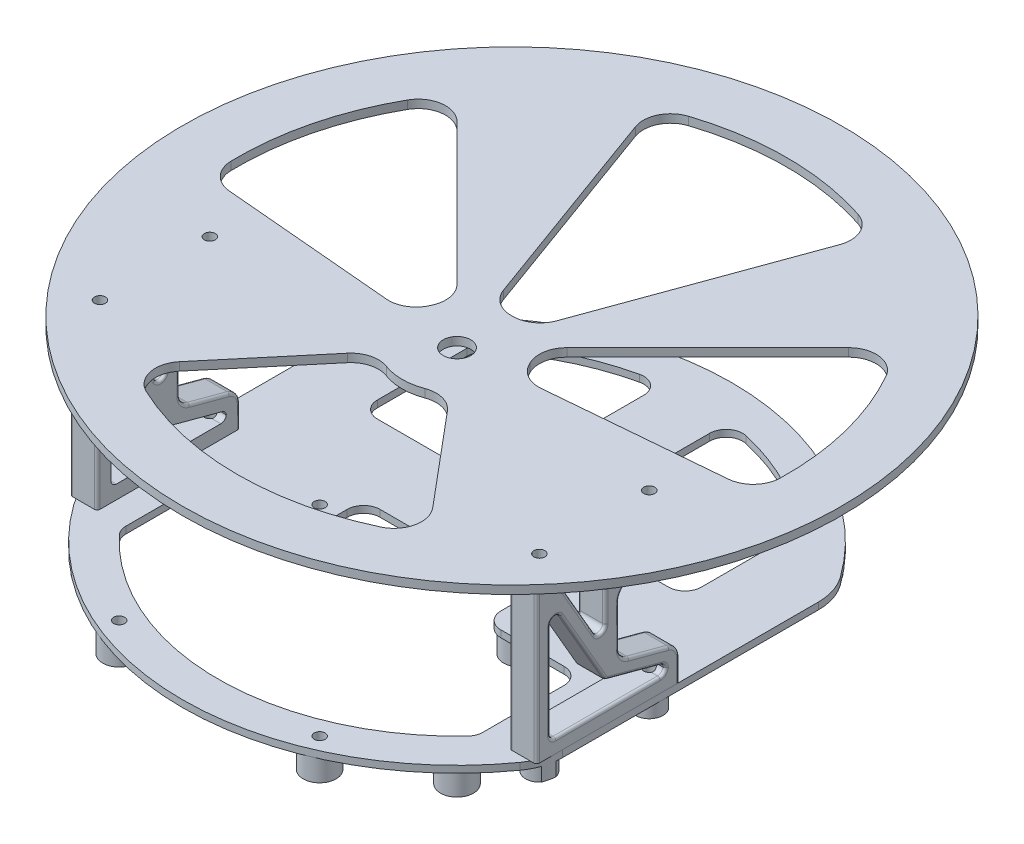
SolidWorks part; units mm, degrees
ref_plane "Front" through (0, 0, 0) normal (0, 0, 1) x (1, 0, 0)
ref_plane "Top" through (0, 0, 0) normal (0, 1, 0) x (1, 0, 0)
ref_plane "Right" through (0, 0, 0) normal (1, 0, 0) x (0, 0, -1)
sketch "Sketch1" plane through (0, 0, 0) normal (0, 1, 0) x (1, 0, 0)
  line L0 (0, 71.1393) -> (0, -87.7098) construction
  line L1 (-42.5, 26.3391) -> (-42.5, -26.3391)
  line L2 (42.5, 26.3391) -> (42.5, -26.3391)
  arc A0 (-42.5, -26.3391) -> (42.5, -26.3391) centre (0, 0) ccw
  arc A1 (42.5, 26.3391) -> (-42.5, 26.3391) centre (0, 0) ccw
  dimension "D1" = 100
  dimension "D2" = 85
extrude "Boss-Extrude1" add sketch "Sketch1" along normal blind 1.25
sketch "Sketch2" plane through (0, 0, 0) normal (0, -1, 0) x (1, 0, 0)
  line L0 (0, 45.5144) -> (0, -63.1722) construction
  line L1 (-51.2989, 0) -> (55.2567, 0) construction
  circle A0 centre (-33, 33) radius 3
  circle A2 centre (-33, 33) radius 1.125
  circle A4 centre (-33, -33) radius 1.125
  circle A5 centre (-33, -33) radius 3
  circle A6 centre (33, -33) radius 3
  circle A7 centre (33, -33) radius 1.125
  circle A8 centre (33, 33) radius 1.125
  circle A9 centre (33, 33) radius 3
  dimension "D3" = 2.25
  dimension "D4" = 6
  dimension "D1" = 66
  dimension "D2" = 66
extrude "Boss-Extrude2" add sketch "Sketch2" along normal blind 4
fillet "Fillet1" radius 10 4 edges at (-42.5, 0.625, -26.3391) (-42.5, 0.625, 26.3391) (42.5, 0.625, -26.3391) (42.5, 0.625, 26.3391)
sketch "Sketch3" plane through (0, 1.25, 0) normal (0, 1, 0) x (1, 0, 0)
  line L0 (0, 58.0627) -> (0, -62.1815) construction
  line L1 (-18.25, -6.75) -> (18.25, -6.75) construction
  line L2 (-18.25, -6.75) -> (-18.25, -43.25) construction
  line L3 (-18.25, -43.25) -> (18.25, -43.25) construction
  line L4 (18.25, -6.75) -> (18.25, -43.25) construction
  line L5 (-18.25, -6.75) -> (18.25, -43.25) construction
  line L6 (-18.25, -43.25) -> (18.25, -6.75) construction
  circle A0 centre (-18.25, -6.75) radius 1
  circle A1 centre (18.25, -6.75) radius 1
  circle A2 centre (18.25, -43.25) radius 1
  circle A3 centre (-18.25, -43.25) radius 1
  circle A4 centre (-40, -5) radius 1
  circle A5 centre (-40, -25) radius 1
  circle A6 centre (40, -25) radius 1
  circle A7 centre (40, -5) radius 1
  point P0 (0, -25)
  dimension "D1" = 2
  dimension "D2" = 36.5
  dimension "D3" = 25
  dimension "D4" = 20
  dimension "D5" = 80
  dimension "D6" = 0
sketch "Sketch4" plane through (0, 0, 0) normal (0, -1, 0) x (1, 0, 0)
  circle A0 centre (-18.25, 43.25) radius 3
  circle A1 centre (18.25, 43.25) radius 3
  circle A2 centre (18.25, 6.75) radius 3
  circle A3 centre (-18.25, 6.75) radius 3
  circle A4 centre (-40, 25) radius 2.5
  circle A5 centre (-40, 5) radius 2.5
  circle A6 centre (40, 25) radius 2.5
  circle A7 centre (40, 5) radius 2.5
  arc M10 (42.5, 23.3184) -> (40.625, 29.1481) centre (32.5, 23.3184) ccw
  arc M16 (-40.625, 29.1481) -> (-42.5, 23.3184) centre (-32.5, 23.3184) ccw
  dimension "D1" = 6
  dimension "D2" = 5
extrude "Boss-Extrude3" add sketch "Sketch4" along normal up to surface (4 mm away) contours A3 | A0 | A1 | A2 region at (-18.25, 0, 43.25) region at (18.25, 0, 43.25) region at (18.25, 0, 6.75) region at (-18.25, 0, 6.75) up to face at (-33, -4, 30)
extrude "Boss-Extrude7" add sketch "Sketch4<3>" along normal offset from surface (2.5 mm away) 1.5 contours A4 M16 | A6 M10 | A5 | A7 region at (-39.9675, 0, 24.9927) region at (39.9675, 0, 24.9927) up to face at (18.25, -4, 3.75)
sketch "Sketch4<3>" plane through (0, 0, 0) normal (0, -1, 0) x (1, 0, 0) same geometry as "Sketch4"
extrude "Cut-Extrude1" cut sketch "Sketch3" against normal through all
sketch "Sketch6" plane through (0, 0, 0) normal (0, -1, 0) x (1, 0, 0)
  line L0 (-29.5, -32.6458) -> (-29.5, -12)
  line L1 (-29.5, -12) -> (-6, -12)
  line L2 (29.5, -12) -> (29.5, -32.6458)
  line L3 (0, 0) -> (0, -57.2909) construction
  line L4 (-32.5, 28.9137) -> (-32.5, 10)
  line L5 (-32.5, 10) -> (-15, 10)
  line L6 (32.5, 10) -> (32.5, 28.9137)
  line L7 (-6, -12) -> (-6, -43.589)
  line L8 (6, -12) -> (6, -43.589)
  line L9 (6, -12) -> (29.5, -12)
  line L10 (15, 10) -> (32.5, 10)
  line L12 (-15, 10) -> (-15, 2)
  line L13 (-15, 2) -> (15, 2)
  line L14 (15, 10) -> (15, 2)
  arc A0 (-29.5, -32.6458) -> (-6, -43.589) centre (0, 0) ccw
  arc A1 (-40.625, -29.1481) -> (40.625, -29.1481) centre (0, 0) ccw construction
  arc A2 (-32.5, 28.9137) -> (32.5, 28.9137) centre (0, 0) cw
  arc A3 (40.625, 29.1481) -> (-40.625, 29.1481) centre (0, 0) ccw construction
  arc A4 (6, -43.589) -> (29.5, -32.6458) centre (0, 0) ccw
  dimension "D2" = 6
  dimension "D4" = 6.5
  dimension "D1" = 59
  dimension "D3" = 12
  dimension "D5" = 10
  dimension "D6" = 12
  dimension "D7" = 65
  dimension "D8" = 8
  dimension "D9" = 30
extrude "Cut-Extrude2" cut sketch "Sketch6" against normal through all
fillet "Fillet2" radius 3 16 edges at (-29.5, 0.625, -12) (-6, 0.625, -12) (-6, 0.625, -43.589) (29.5, 0.625, -12) (29.5, 0.625, -32.6458) (6, 0.625, -43.589) (6, 0.625, -12) (-29.5, 0.625, -32.6458) (32.5, 0.625, 28.9137) (-32.5, 0.625, 28.9137) (-32.5, 0.625, 10) (32.5, 0.625, 10) (15, 0.625, 2) (15, 0.625, 10) (-15, 0.625, 2) (-15, 0.625, 10)
ref_point "Point1"
ref_plane "Plane1" through (-40, 0, 0) normal (-1, 0, 0) x (0, 0, 1)
sketch "Sketch7" plane through (-40, 0, 0) normal (-1, 0, 0) x (0, 0, 1)
  line L0 (2, 1.25) -> (2, 7.25)
  line L1 (-23.3184, 1.25) -> (23.3184, 1.25) construction
  line L2 (2, 7.25) -> (13, 10.1974)
  line L3 (13, 10.1974) -> (13, 21.3026)
  line L4 (13, 21.3026) -> (2, 24.25)
  line L5 (2, 24.25) -> (2, 30.25)
  line L6 (2, 30.25) -> (28, 30.25)
  line L7 (28, 30.25) -> (28, 1.25)
  line L8 (28, 1.25) -> (2, 1.25)
  line L9 (4.5, 27.75) -> (23.8548, 27.75)
  line L11 (25.5, 3.75) -> (4.5, 3.75)
  line L12 (4.5, 3.75) -> (4.5, 5.3317)
  line L13 (4.5, 5.3317) -> (15.5, 8.2791)
  line L14 (15.5, 13.2791) -> (15.5, 23.2209)
  line L15 (15.5, 23.2209) -> (4.5, 26.1683)
  line L16 (4.5, 26.1683) -> (4.5, 27.75)
  line L17 (15.5, 8.2791) -> (25.5, 25.5996)
  line L19 (23.8548, 27.75) -> (15.5, 13.2791)
  line L21 (15.5, 8.2791) -> (15.5, 23.2209) construction
  line L22 (25.5, 25.5996) -> (25.5, 3.75)
  line L23 (25.5, 27.75) -> (25.5, 3.75) construction
  line L24 (4.5, 27.75) -> (25.5, 27.75) construction
  dimension "D1" = 2
  dimension "D2" = 26
  dimension "D3" = 15
  dimension "D4" = 15
  dimension "D5" = 15
  dimension "D6" = 6
  dimension "D7" = 29
  dimension "D9" = 2.5
  dimension "D10" = 30
  dimension "D8" = 2.5
extrude "Boss-Extrude4" add sketch "Sketch7" along normal mid plane 5 separate body
fillet "Fillet3" radius 2.5 4 edges at (-40, 7.25, 2) (-40, 10.1974, 13) (-40, 21.3026, 13) (-40, 24.25, 2)
fillet "Fillet4" radius 1 10 edges at (-40, 25.5996, 25.5) (-40, 8.2791, 15.5) (-40, 5.3317, 4.5) (-40, 3.75, 25.5) (-40, 3.75, 4.5) (-40, 13.2791, 15.5) (-40, 27.75, 4.5) (-40, 26.1683, 4.5) (-40, 23.2209, 15.5) (-40, 27.75, 23.8548)
fillet "Fillet5" radius 0.5 47 edges at (-37.5, 15.75, 28) (-37.5, 3.2908, 2) (-37.5, 6.8536, 2.5166) (-37.5, 8.7237, 7.5) (-37.5, 10.5939, 12.4834) (-37.5, 15.75, 13) (-37.5, 20.9061, 12.4834) (-37.5, 22.7763, 7.5) (-37.5, 24.6464, 2.5166) (-37.5, 28.2092, 2) (-42.5, 3.2908, 2) (-42.5, 6.8536, 2.5166) (-42.5, 8.7237, 7.5) (-42.5, 10.5939, 12.4834) (-42.5, 15.75, 13) (-42.5, 20.9061, 12.4834) (-42.5, 22.7763, 7.5) (-42.5, 24.6464, 2.5166) (-42.5, 28.2092, 2) (-42.5, 15.75, 28) (-42.5, 4.0108, 4.8265) (-42.5, 5.2093, 4.7358) (-42.5, 6.8511, 10.1705) (-42.5, 8.3445, 15.4498) (-42.5, 15.5027, 19.6705) (-42.5, 22.8335, 24.7588) (-42.5, 13.3088, 25.5) (-42.5, 4.0429, 25.2071) (-42.5, 3.75, 15) (-37.5, 27.4892, 4.8265) (-42.5, 27.4892, 4.8265) (-37.5, 26.2907, 4.7358) (-37.5, 24.6946, 10) (-37.5, 23.0623, 15.2934) (-37.5, 19.7324, 15.5) (-37.5, 16.0452, 16.2412) (-42.5, 26.2907, 4.7358) (-42.5, 24.6946, 10) (-42.5, 23.0623, 15.2934) (-42.5, 19.7324, 15.5) (-42.5, 16.0452, 16.2412) (-37.5, 27.75, 13.8114) (-42.5, 27.75, 13.8114) (-37.5, 21.3806, 20.1774) (-42.5, 21.3806, 20.1774) (-37.5, 27.25, 22.9887) (-42.5, 27.25, 22.9887)
sketch "Sketch8" plane through (0, 1.25, 0) normal (0, -1, 0) x (1, 0, 0)
  circle A2 centre (-40, 5) radius 1
  circle A3 centre (-40, 25) radius 1
extrude "Cut-Extrude3" cut sketch "Sketch8" against normal blind 3.5
extrude "Cut-Extrude4" cut sketch "Sketch8<3>" along normal blind 3.5 from surface starting at face at (-40, 30.25, 15)
sketch "Sketch8<3>" plane through (0, 1.25, 0) normal (0, -1, 0) x (1, 0, 0) same geometry as "Sketch8"
mirror "Mirror1" about plane through (0, 0, 0) normal (1, 0, 0) of bodies 109
sketch "Sketch9" plane through (0, 30.25, 0) normal (0, 1, 0) x (1, 0, 0)
  line L0 (-42.5, 23.3184) -> (-42.5, -23.3184) construction
  line L1 (42.5, -23.3184) -> (42.5, 23.3184) construction
  line L2 (-42.5, 23.3184) -> (-42.5, -23.3184) construction
  line L3 (42.5, -23.3184) -> (42.5, 23.3184) construction
  arc A0 (40.625, 29.1481) -> (-40.625, 29.1481) centre (0, 0) ccw construction
  arc A1 (-40.625, 29.1481) -> (-42.5, 23.3184) centre (-32.5, 23.3184) ccw construction
  arc A2 (-42.5, -23.3184) -> (-40.625, -29.1481) centre (-32.5, -23.3184) ccw construction
  arc A3 (-40.625, -29.1481) -> (40.625, -29.1481) centre (0, 0) ccw construction
  arc A4 (40.625, -29.1481) -> (42.5, -23.3184) centre (32.5, -23.3184) ccw construction
  arc A5 (42.5, 23.3184) -> (40.625, 29.1481) centre (32.5, 23.3184) ccw construction
  arc A6 (-40.625, 29.1481) -> (-42.5, 23.3184) centre (-32.5, 23.3184) ccw construction
  arc A7 (-42.5, -23.3184) -> (-40.625, -29.1481) centre (-32.5, -23.3184) ccw construction
  arc A8 (-40.625, -29.1481) -> (40.625, -29.1481) centre (0, 0) ccw construction
  arc A9 (40.625, -29.1481) -> (42.5, -23.3184) centre (32.5, -23.3184) ccw construction
  arc A10 (42.5, 23.3184) -> (40.625, 29.1481) centre (32.5, 23.3184) ccw construction
  arc A11 (40.625, 29.1481) -> (-40.625, 29.1481) centre (0, 0) ccw construction
  circle A14 centre (0, 10) radius 60
  dimension "D1" = 120
  dimension "D2" = 10
extrude "Boss-Extrude6" add sketch "Sketch9" along normal blind 1.5 separate body
sketch "Sketch12" plane through (0, 31.75, 0) normal (0, 1, 0) x (1, 0, 0)
  circle A0 centre (40, -5) radius 1 construction
  circle A1 centre (40, -25) radius 1 construction
  circle A2 centre (-40, -5) radius 1 construction
  circle A3 centre (-40, -25) radius 1 construction
  circle A4 centre (40, -5) radius 1
  circle A5 centre (40, -25) radius 1
  circle A6 centre (-40, -5) radius 1
  circle A7 centre (-40, -25) radius 1
  circle A8 centre (0, 0) radius 2.5
  dimension "D1" = 5
extrude "Cut-Extrude7" cut sketch "Sketch12" against normal up to next (1.5 mm away)
sketch "Sketch13" plane through (0, 31.75, 0) normal (0, 1, 0) x (1, 0, 0)
  line L0 (0, 0) -> (0, 60) construction
  line L1 (-3.4202, 9.3969) -> (-20.2749, 55.7048)
  line L2 (-9.9619, 0.8716) -> (-49.6793, 4.3464)
  line L3 (-7.0711, 7.0711) -> (-40, 40)
  line L4 (3.4202, 9.3969) -> (20.2749, 55.7048)
  line L5 (7.0711, 7.0711) -> (40, 40)
  line L6 (9.9619, 0.8716) -> (49.6793, 4.3464)
  line L7 (-6.4279, -7.6604) -> (-26.9487, -32.1162)
  line L8 (6.4279, -7.6604) -> (26.9487, -32.1162)
  arc A0 (-6.4279, -7.6604) -> (6.4279, -7.6604) centre (0, 0) ccw
  arc A1 (-40, 40) -> (-49.6793, 4.3464) centre (0, 10) ccw
  arc A2 (20.2749, 55.7048) -> (-20.2749, 55.7048) centre (0, 10) ccw
  arc A3 (49.6793, 4.3464) -> (40, 40) centre (0, 10) ccw
  arc A4 (-26.9487, -32.1162) -> (26.9487, -32.1162) centre (0, 10) ccw
  arc A5 (9.9619, 0.8716) -> (7.0711, 7.0711) centre (0, 0) ccw
  arc A6 (3.4202, 9.3969) -> (-3.4202, 9.3969) centre (0, 0) ccw
  arc A7 (-7.0711, 7.0711) -> (-9.9619, 0.8716) centre (0, 0) ccw
  dimension "D1" = 100
  dimension "D5" = 20
  dimension "D2" = 40
  dimension "D3" = 40
  dimension "D4" = 25
  dimension "D6" = 80
extrude "Cut-Extrude8" cut sketch "Sketch13" against normal up to next (1.5 mm away)
fillet "Fillet6" radius 5 16 edges at (-20.2749, 31, -55.7048) (3.4202, 31, -9.3969) (-3.4202, 31, -9.3969) (40, 31, -40) (49.6793, 31, -4.3464) (9.9619, 31, -0.8716) (7.0711, 31, -7.0711) (26.9487, 31, 32.1162) (-26.9487, 31, 32.1162) (-6.4279, 31, 7.6604) (6.4279, 31, 7.6604) (20.2749, 31, -55.7048) (-49.6793, 31, -4.3464) (-7.0711, 31, -7.0711) (-9.9619, 31, -0.8716) (-40, 31, -40)
equation "\"D5@Sketch7\"=\"D4@Sketch7\""
